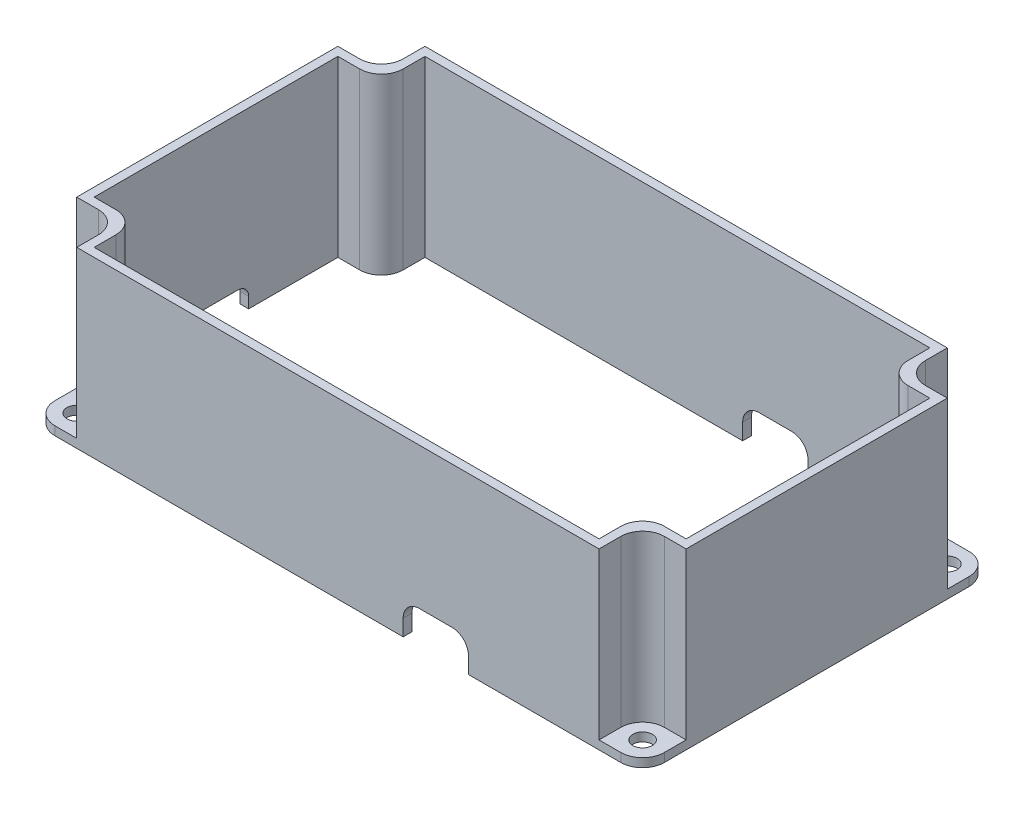
SolidWorks part; units mm, degrees
ref_plane "Front Plane" through (0, 0, 0) normal (0, 0, 1) x (1, 0, 0)
ref_plane "Top Plane" through (0, 0, 0) normal (0, 1, 0) x (1, 0, 0)
ref_plane "Right Plane" through (0, 0, 0) normal (1, 0, 0) x (0, 0, -1)
sketch "Sketch1" plane through (0, 0, 0) normal (0, 1, 0) x (1, 0, 0)
  line L0 (70, 30) -> (60, 30)
  line L1 (-70, 40) -> (70, 40)
  line L2 (-70, 40) -> (-70, -40)
  line L3 (-70, -40) -> (70, -40)
  line L4 (70, 40) -> (70, -40)
  line L5 (-70, 40) -> (70, -40) construction
  line L6 (-70, -40) -> (70, 40) construction
  line L7 (60, 30) -> (60, 40)
  line L8 (0, 0) -> (26.6657, 0) construction
  line L9 (0, 0) -> (0, 20) construction
  line L10 (58, 40) -> (58, 28)
  line L11 (58, 28) -> (70, 28)
  line L12 (-60, 40) -> (-70, 30) construction
  line L13 (-60, 30) -> (-70, 40) construction
  line L14 (-58, 28) -> (-70, 28)
  line L15 (-58, 40) -> (-58, 28)
  line L16 (60, 30) -> (70, 40) construction
  line L17 (60, 40) -> (70, 30) construction
  line L18 (-60, 30) -> (-60, 40)
  line L19 (-70, 30) -> (-60, 30)
  line L20 (60, -40) -> (70, -30) construction
  line L21 (60, -30) -> (70, -40) construction
  line L22 (-60, -30) -> (-70, -40) construction
  line L23 (-60, -40) -> (-70, -30) construction
  line L24 (-70, -30) -> (-60, -30)
  line L25 (-60, -30) -> (-60, -40)
  line L26 (-58, -40) -> (-58, -28)
  line L27 (-58, -28) -> (-70, -28)
  line L28 (58, -28) -> (70, -28)
  line L29 (58, -40) -> (58, -28)
  line L30 (60, -30) -> (60, -40)
  line L31 (70, -30) -> (60, -30)
  line L32 (-68, 28) -> (-68, -28)
  line L33 (-58, -38) -> (58, -38)
  line L34 (68, 28) -> (68, -28)
  line L35 (58, 38) -> (-58, 38)
  circle A0 centre (65, 35) radius 2.25
  circle A1 centre (-65, 35) radius 2.25
  circle A2 centre (-65, -35) radius 2.25
  circle A3 centre (65, -35) radius 2.25
  point P0 (0, 0)
  dimension "D4" = 4.5
  dimension "D1" = 80
  dimension "D2" = 140
  dimension "D3" = 10
  dimension "D5" = 2
  dimension "D6" = 2
  dimension "D7" = 2
  dimension "D8" = 2
  dimension "D9" = 2
extrude "Boss-Extrude6" add sketch "Sketch1" along normal blind 40 contours L33 L26 L3 L29 | L31 L4 L28 L29 L3 L30 | L11 L34 L28 L4 | L10 L11 L4 L0 L7 L1 | L35 L10 L1 L15 | L19 L2 L14 L15 L1 L18 | L32 L14 L2 L27 | L26 L27 L2 L24 L25 L3 region at (69.8303, 0, -29) region at (69, 0, 0) region at (69.8303, 0, 29) region at (0, 0, -39) region at (-58.1697, 0, -39) region at (0, 0, 39) region at (-58.1697, 0, 39) region at (-69, 0, 0)
extrude "Boss-Extrude7" add sketch "Sketch1<7>" along normal blind 2 contours L25 L24 L2 L3 A2 | L4 L31 L30 L3 A3 | L7 L0 L4 L1 A0 | L2 L19 L18 L1 A1 region at (65, 0, -30.1414) region at (69.8586, 0, 35) region at (-60.1414, 0, -35) region at (-65, 0, 39.8586)
sketch "Sketch1<7>" plane through (0, 0, 0) normal (0, 1, 0) x (1, 0, 0) same geometry as "Sketch1"
fillet "Fillet1" radius 5 12 edges at (-70, 1, 40) (-70, 1, -40) (70, 1, -40) (70, 1, 40) (-60, 21, 30) (60, 21, 30) (58, 20, 28) (58, 20, -28) (60, 21, -30) (-58, 20, 28) (-58, 20, -28) (-60, 21, -30)
sketch "Sketch2" plane through (0, 0, -40) normal (0, 0, -1) x (-1, 0, 0)
  line L0 (65, 0) -> (-65, 0) construction
  line L1 (-30, 0) -> (-15, 0)
  line L2 (-30, 0) -> (-30, 3.75)
  line L3 (-26.25, 7.5) -> (-18.75, 7.5)
  line L4 (-15, 0) -> (-15, 3.75)
  line L5 (-60, 40) -> (-60, 2) construction
  arc A0 (-18.75, 7.5) -> (-15, 3.75) centre (-18.75, 3.75) cw
  arc A1 (-30, 3.75) -> (-26.25, 7.5) centre (-26.25, 3.75) cw
  point P10 (-15, 7.5)
  point P13 (-30, 7.5)
  dimension "D4" = 3.75
  dimension "D1" = 7.5
  dimension "D2" = 15
  dimension "D3" = 30
extrude "Cut-Extrude1" cut sketch "Sketch2" against normal through all
sketch "Sketch3" plane through (-70, 0, 0) normal (-1, 0, 0) x (0, 0, 1)
  line L0 (-35, 0) -> (35, 0) construction
  line L1 (-7.5, 0) -> (7.5, 0)
  line L2 (-7.5, 0) -> (-7.5, 2.5)
  line L3 (-5, 5) -> (5, 5)
  line L4 (7.5, 0) -> (7.5, 2.5)
  arc A0 (5, 5) -> (7.5, 2.5) centre (5, 2.5) cw
  arc A1 (-7.5, 2.5) -> (-5, 5) centre (-5, 2.5) cw
  point P6 (0, 0)
  point P10 (7.5, 5)
  point P13 (-7.5, 5)
  dimension "D3" = 2.5
  dimension "D1" = 5
  dimension "D2" = 15
extrude "Cut-Extrude2" cut sketch "Sketch3" against normal up to next
